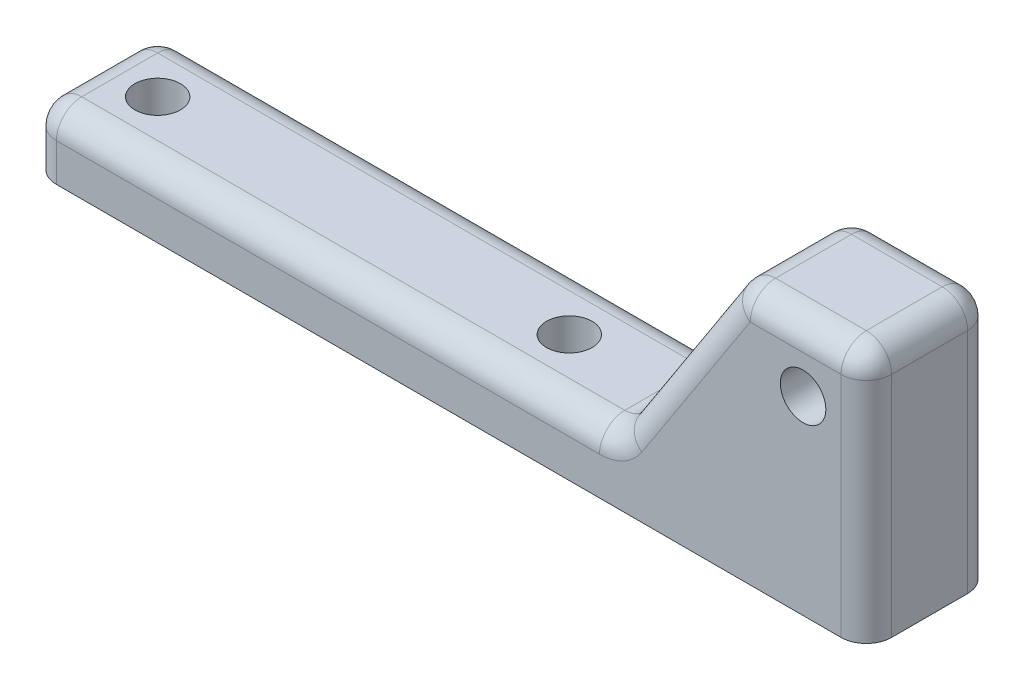
SolidWorks part; units mm, degrees
ref_plane "Front Plane" through (0, 0, 0) normal (0, 0, 1) x (1, 0, 0)
ref_plane "Top Plane" through (0, 0, 0) normal (0, 1, 0) x (1, 0, 0)
ref_plane "Right Plane" through (0, 0, 0) normal (1, 0, 0) x (0, 0, -1)
sketch "Sketch1" plane through (0, 0, 0) normal (0, 1, 0) x (1, 0, 0)
  line L1 (0, 0) -> (83.82, 0)
  line L2 (0, 0) -> (0, 12.7)
  line L3 (0, 12.7) -> (83.82, 12.7)
  line L4 (83.82, 0) -> (83.82, 12.7)
  circle A0 centre (6.35, 6.35) radius 2.286
  circle A1 centre (47.6592, 6.35) radius 2.286
  point P9 (0, 6.35)
  dimension "D3" = 4.572
  dimension "D1" = 6.35
  dimension "D2" = 12.7
  dimension "D4" = 41.3092
  dimension "D5" = 83.82
extrude "Boss-Extrude1" add sketch "Sketch1" along normal blind 25.4
sketch "Sketch2" plane through (0, 0, 0) normal (0, 0, 1) x (1, 0, 0)
  line L0 (83.82, 25.4) -> (83.82, 0) construction
  line L2 (0, 0) -> (83.82, 0) construction
  circle A0 centre (77.47, 19.05) radius 2.286
  dimension "D2" = 4.572
  dimension "D1" = 6.35
  dimension "D3" = 19.05
extrude "Cut-Extrude1" cut sketch "Sketch2" against normal blind 12.7
fillet "Fillet1" radius 2.54 4 edges at (83.82, 12.7, -12.7) (83.82, 12.7, 0) (0, 12.7, -12.7) (0, 12.7, 0)
sketch "Sketch3" plane through (0, 0, 0) normal (0, 0, 1) x (1, 0, 0)
  line L0 (2.54, 0) -> (81.28, 0) construction
  line L1 (0, 25.4) -> (71.12, 25.4)
  line L2 (0, 25.4) -> (0, 6.35)
  line L3 (0, 6.35) -> (71.12, 6.35)
  line L4 (71.12, 25.4) -> (71.12, 6.35)
  line L5 (83.82, 25.4) -> (83.82, 0) construction
  dimension "D1" = 6.35
  dimension "D2" = 12.7
extrude "Cut-Extrude2" cut sketch "Sketch3" against normal through all
chamfer "Chamfer1" distance 12.7 angle 57 1 edges at (71.12, 6.35, -6.35) first distance on face at (8.636, 6.35, -6.35)
fillet "Fillet2" radius 2.54 14 edges at (64.6056, 15.875, 0) (64.6056, 15.875, -12.7) (30.48, 6.35, 0) (0.7439, 6.35, -0.7439) (0, 6.35, -6.35) (0.7439, 6.35, -11.9561) (83.0761, 25.4, -11.9561) (83.82, 25.4, -6.35) (83.0761, 25.4, -0.7439) (76.0356, 25.4, 0) (70.7912, 25.4, -6.35) (76.0356, 25.4, -12.7) (30.48, 6.35, -12.7) (58.42, 6.35, -6.35)
